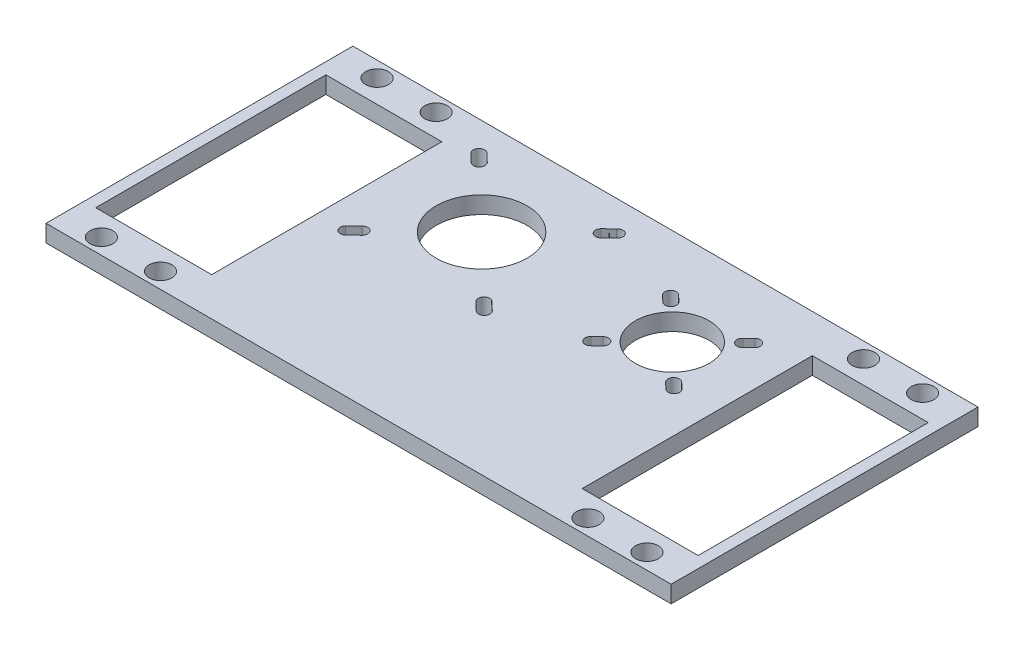
SolidWorks part; units mm, degrees
ref_plane "Plan de face" through (0, 0, 0) normal (0, 0, 1) x (1, 0, 0)
ref_plane "Plan de dessus" through (0, 0, 0) normal (0, 1, 0) x (1, 0, 0)
ref_plane "Plan de droite" through (0, 0, 0) normal (1, 0, 0) x (0, 0, -1)
sketch "Esquisse1" plane through (0, 0, 0) normal (0, 1, 0) x (1, 0, 0)
  line L1 (-54, 35.0217) -> (56, 35.0217)
  line L2 (-54, 35.0217) -> (-54, -18.9783)
  line L3 (-54, -18.9783) -> (56, -18.9783)
  line L4 (56, 35.0217) -> (56, -18.9783)
  dimension "D1" = 54
  dimension "D2" = 110
extrude "Boss.-Extru.1" add sketch "Esquisse1" along normal blind 3
sketch "Esquisse2" plane through (0, 3, 0) normal (0, 1, 0) x (1, 0, 0)
  line L0 (56, 35.0217) -> (-54, 35.0217) construction
  line L1 (-52, 28.2717) -> (-31.6, 28.2717)
  line L2 (-52, 28.2717) -> (-52, -12.2283)
  line L3 (-52, -12.2283) -> (-31.6, -12.2283)
  line L4 (-31.6, 28.2717) -> (-31.6, -12.2283)
  line L6 (-54, 35.0217) -> (-54, -18.9783) construction
  line L7 (33.6, 28.2717) -> (54, 28.2717)
  line L8 (33.6, 28.2717) -> (33.6, -12.2283)
  line L9 (33.6, -12.2283) -> (54, -12.2283)
  line L10 (54, 28.2717) -> (54, -12.2283)
  line L11 (56, -18.9783) -> (56, 35.0217) construction
  circle A0 centre (-47, 32.2717) radius 2
  circle A1 centre (-36.6, 32.2717) radius 2
  circle A2 centre (-47, -16.2283) radius 2
  circle A3 centre (-36.6, -16.2283) radius 2
  circle A4 centre (38.6, 32.2717) radius 2
  circle A5 centre (49, 32.2717) radius 2
  circle A6 centre (38.6, -16.2283) radius 2
  circle A7 centre (49, -16.2283) radius 2
  dimension "D7" = 4
  dimension "D8" = 4
  dimension "D9" = 4
  dimension "D10" = 4
  dimension "D21" = 4
  dimension "D22" = 4
  dimension "D23" = 4
  dimension "D24" = 4
  dimension "D1" = 40.5
  dimension "D2" = 20.4
  dimension "D3" = 6.75
  dimension "D4" = 2
  dimension "D5" = 4
  dimension "D6" = 4
  dimension "D11" = 4
  dimension "D12" = 4
  dimension "D13" = 5
  dimension "D14" = 5
  dimension "D15" = 5
  dimension "D16" = 5
  dimension "D17" = 40.5
  dimension "D18" = 20.4
  dimension "D19" = 4
  dimension "D20" = 4
  dimension "D25" = 4
  dimension "D26" = 4
  dimension "D27" = 5
  dimension "D28" = 5
  dimension "D29" = 5
  dimension "D30" = 5
  dimension "D31" = 2
  dimension "D32" = 6.75
extrude "Enlèv. mat.-Extru.1" cut sketch "Esquisse2" against normal blind 46
sketch "Esquisse3" plane through (0, 3, 0) normal (0, 1, 0) x (1, 0, 0)
  line L0 (-4.2842, 6.9571) -> (-2.7941, 5.5204)
  line L5 (26.6, 25.1266) -> (25.518, 24.0877) construction
  line L6 (-41.8001, 18.0218) -> (43.7999, 18.0218) construction
  line L7 (27.2926, 24.4052) -> (26.2105, 23.3664)
  line L8 (-4.3393, 29.0362) -> (-2.9466, 30.3684)
  line L9 (-2.9466, 29.0852) -> (-2.9466, 29.0788)
  line L10 (-2.9466, 27.6021) -> (-1.4865, 29.0059)
  line L11 (33.6, 28.2717) -> (33.6, -12.2283) construction
  line L12 (-25.9157, 5.5204) -> (-24.3881, 6.9802)
  line L13 (-1.4068, 6.9611) -> (-2.8532, 8.3521)
  line L14 (-2.1, 6.2403) -> (-1.3792, 5.5471)
  line L15 (-25.7698, 6.9802) -> (-25.7722, 6.9802)
  line L16 (-27.2687, 6.9802) -> (-25.7698, 8.4262)
  line L17 (9.8, 27.0468) -> (28.6, 8.9968)
  line L18 (-27.2932, 29.0825) -> (-25.8517, 27.6962)
  line L19 (-25.8869, 29.1021) -> (-25.8873, 29.1178)
  line L20 (-25.9229, 30.5392) -> (-24.4654, 29.1378)
  line L21 (9.8, 27.0468) -> (28.6, 27.0468)
  line L22 (-25.8873, 29.1178) -> (-25.8792, 29.1101)
  line L23 (9.8, 27.0468) -> (9.8, 8.9968)
  line L24 (9.8, 8.9968) -> (28.6, 8.9968)
  line L25 (28.6, 27.0468) -> (28.6, 8.9968)
  line L26 (9.8, 8.9968) -> (28.6, 27.0468)
  line L27 (25.9074, 25.8479) -> (24.8254, 24.8091)
  line L28 (26.5169, 10.9968) -> (25.4349, 12.0357) construction
  line L29 (25.8243, 10.2755) -> (24.7423, 11.3143)
  line L30 (27.2095, 11.7182) -> (26.1274, 12.757)
  line L31 (11.8831, 10.9968) -> (12.9651, 12.0357) construction
  line L32 (11.1905, 11.7182) -> (12.2726, 12.757)
  line L33 (12.5757, 10.2755) -> (13.6577, 11.3143)
  line L34 (11.8831, 25.0468) -> (12.9651, 24.0079) construction
  line L35 (12.5757, 25.7682) -> (13.6577, 24.7293)
  line L36 (11.1905, 24.3255) -> (12.2726, 23.2866)
  circle A0 centre (-14.35, 18.0218) radius 8
  arc A1 (-2.7941, 5.5204) -> (-1.4068, 6.9611) centre (-2.1, 6.2403) ccw
  arc A2 (-2.9466, 29.0852) -> (-2.9003, 29.0336) centre (-2.1795, 29.7268) ccw
  arc A3 (-27.1565, 7.0884) -> (-25.7523, 5.6765) centre (-26.5205, 6.3168) ccw
  arc A4 (-25.8869, 29.1022) -> (-25.8792, 29.1101) centre (-26.6, 29.8033) ccw
  arc A5 (-25.8517, 27.6962) -> (-24.4654, 29.1378) centre (-25.1585, 28.4169) ccw
  arc A7 (-4.2842, 29.0889) -> (-2.9098, 27.6375) centre (-3.621, 28.3404) ccw
  arc A8 (-2.8435, 8.3428) -> (-4.1835, 6.86) centre (-3.5415, 7.6267) ccw
  arc A9 (-1.4865, 29.0059) -> (-2.9466, 30.3684) centre (-2.1795, 29.7268) ccw
  arc A10 (-2.9003, 29.0336) -> (-2.9466, 29.0788) centre (-3.621, 28.3404) ccw
  arc A11 (-24.3881, 6.9802) -> (-25.7766, 8.4196) centre (-25.079, 7.7032) ccw
  arc A12 (-25.8792, 29.1101) -> (-25.8869, 29.1021) centre (-25.1585, 28.4169) ccw
  arc A13 (-25.8912, 30.5087) -> (-27.2932, 29.0825) centre (-26.6, 29.8033) ccw
  circle A14 centre (19.2, 18.0218) radius 6.5
  arc A15 (27.2926, 24.4052) -> (25.9074, 25.8479) centre (26.6, 25.1266) ccw
  arc A16 (24.8254, 24.8091) -> (26.2105, 23.3664) centre (25.518, 24.0877) ccw
  arc A17 (25.8243, 10.2755) -> (27.2095, 11.7182) centre (26.5169, 10.9968) ccw
  arc A18 (26.1274, 12.757) -> (24.7423, 11.3143) centre (25.4349, 12.0357) ccw
  arc A19 (11.1905, 11.7182) -> (12.5757, 10.2755) centre (11.8831, 10.9968) ccw
  arc A20 (13.6577, 11.3143) -> (12.2726, 12.757) centre (12.9651, 12.0357) ccw
  arc A21 (12.5757, 25.7682) -> (11.1905, 24.3255) centre (11.8831, 25.0468) ccw
  arc A22 (12.2726, 23.2866) -> (13.6577, 24.7293) centre (12.9651, 24.0079) ccw
  point P6 (26.059, 24.6072)
  point P63 (25.9759, 11.5162)
  point P70 (12.4241, 11.5162)
  point P75 (12.4241, 24.5274)
  dimension "D5" = 16
  dimension "D10" = 2
  dimension "D11" = 2
  dimension "D12" = 2
  dimension "D13" = 2
  dimension "D14" = 1
  dimension "D15" = 2
  dimension "D16" = 2
  dimension "D17" = 2
  dimension "D18" = 2
  dimension "D2" = 13
  dimension "D3" = 14.4
  dimension "D7" = 1
  dimension "D20" = 1
  dimension "D21" = 1
  dimension "D4" = 18.8
  dimension "D6" = 18.05
  dimension "D8" = 1.5
  dimension "D9" = 2
  dimension "D19" = 1.5
  dimension "D22" = 1.5
  dimension "D23" = 1.5
  dimension "D24" = 2
  dimension "D25" = 2
extrude "Enlèv. mat.-Extru.2" cut sketch "Esquisse3" against normal blind 10 contours L10 A9 L8 A7 A2 A10 L9 | A0 | L20 A13 L18 A5 L22 A12 L19 | L12 A11 L16 A3 | L13 A8 L0 A1 region at (-2.8204, 3, -6.9337) region at (-2.8998, 3, -29.0329) region at (-25.7997, 3, -7.0107) region at (-25.8793, 3, -29.1101) region at (-14.35, 3, -18.0218)
extrude "Enlèv. mat.-Extru.3" cut sketch "Esquisse3<3>" against normal blind 15 contours L17 A22 L35 A21 | L36 A22 L17 A21 | L27 A16 L26 A15 | L26 A16 L7 A15 | L26 A20 L32 A19 | L33 A20 L26 A19 | L30 A18 L17 A17 | L17 A18 L29 A17 | A14 region at (26.3785, 3, -24.2744) region at (25.7395, 3, -24.9399) region at (12.7436, 3, -24.8602) region at (12.1046, 3, -24.1946) region at (25.6564, 3, -11.1835) region at (26.2954, 3, -11.849) region at (12.1046, 3, -11.849) region at (12.7436, 3, -11.1835)
sketch "Esquisse3<3>" plane through (0, 3, 0) normal (0, 1, 0) x (1, 0, 0) same geometry as "Esquisse3"
